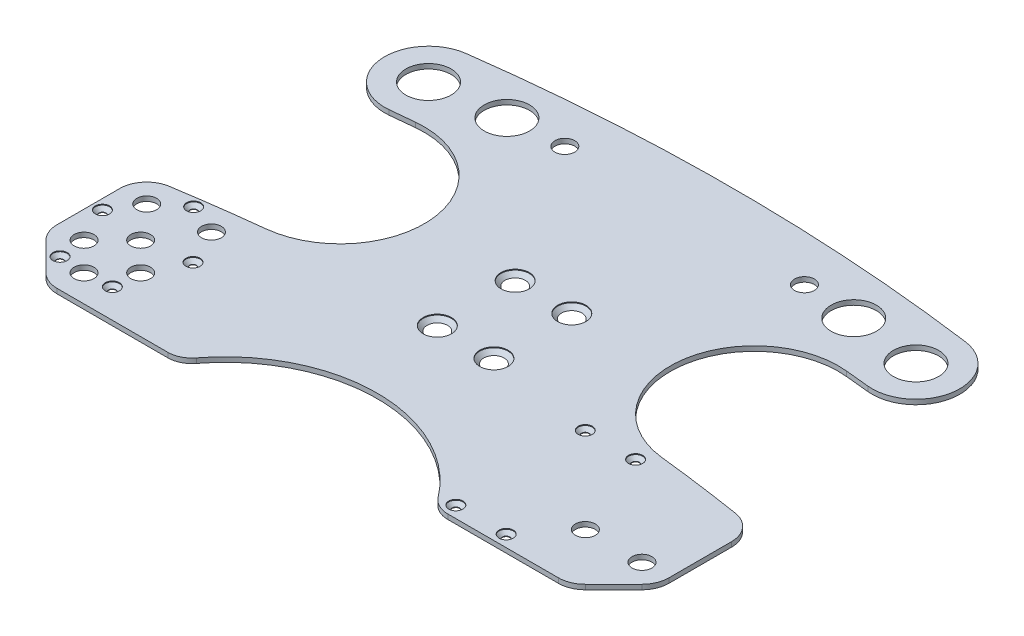
SolidWorks part; units mm, degrees
ref_plane "Front Plane" through (0, 0, 0) normal (0, 0, 1) x (1, 0, 0)
ref_plane "Top Plane" through (0, 0, 0) normal (0, 1, 0) x (1, 0, 0)
ref_plane "Right Plane" through (0, 0, 0) normal (1, 0, 0) x (0, 0, -1)
sketch "Sketch1" plane through (0, 0, 0) normal (0, 1, 0) x (1, 0, 0)
  line L1 (-120, -95) -> (120, -95)
  line L2 (-120, -95) -> (-120, 95)
  line L3 (-120, 95) -> (120, 95)
  line L4 (120, -95) -> (120, 95)
  line L5 (-120, -95) -> (120, 95) construction
  line L6 (-120, 95) -> (120, -95) construction
  line L7 (-10, 13.75) -> (10, 13.75)
  line L8 (-10, 13.75) -> (-10, -13.75)
  line L9 (-10, -13.75) -> (10, -13.75)
  line L10 (10, 13.75) -> (10, -13.75)
  line L11 (-10, 13.75) -> (10, -13.75) construction
  line L12 (-10, -13.75) -> (10, 13.75) construction
  circle A0 centre (0, 0) radius 95
  circle A1 centre (-10, 13.75) radius 2.5
  circle A2 centre (10, 13.75) radius 2.5
  circle A3 centre (10, -13.75) radius 2.5
  circle A4 centre (-10, -13.75) radius 2.5
  circle A5 centre (0, 0) radius 120
  dimension "D3" = 5
  dimension "D1" = 240
  dimension "D2" = 190
  dimension "D4" = 27.5
  dimension "D5" = 20
extrude "Boss-Extrude1" add sketch "Sketch1" along normal blind 1.7 contours A0 A4 L8 A1 L7 A2 L10 A3 L9 | A4 L9 A3 L10 A2 L7 A1 L8 | L3 A5 L1 A0 | L1 A5 L3 A0 region at (-105.6812, 0, 51.9346) region at (68.7642, 0, 68.7642) region at (-92.313, 0, 0) region at (0, 0, 0)
sketch "Sketch2" plane through (0, 1.7, 0) normal (0, 1, 0) x (1, 0, 0)
  line L0 (-81.1673, -40) -> (21.9115, -40) construction
  line L1 (-127.3056, -60) -> (138.909, -60) construction
  line L2 (-88.5406, 28.139) -> (-88.5406, -89.0376) construction
  line L3 (-88.5406, -40) -> (-88.5406, -60) construction
  line L4 (0, 21.6044) -> (0, -21.4213) construction
  line L5 (88.5406, 33.139) -> (88.5406, -84.0376) construction
  line L6 (-151.9803, -25) -> (55.006, -25) construction
  line L7 (-48.8837, 35) -> (62.426, 35) construction
  circle A0 centre (0, 0) radius 35
  circle A1 centre (0, 35) radius 2.5
  circle A2 centre (30.3109, 17.5) radius 2.5
  circle A3 centre (30.3109, -17.5) radius 2.5
  circle A4 centre (0, -35) radius 2.5
  circle A5 centre (-30.3109, -17.5) radius 2.5
  circle A6 centre (-30.3109, 17.5) radius 2.5
  circle A7 centre (-88.5406, -40) radius 3.5
  circle A8 centre (-88.5406, -50) radius 10
  circle A9 centre (-78.5406, -50) radius 3.5
  circle A10 centre (-88.5406, -60) radius 3.5
  circle A11 centre (-98.5406, -50) radius 3.5
  circle A12 centre (78.5406, -50) radius 3.5
  circle A13 centre (98.5406, -50) radius 3.5
  circle A14 centre (-98.5406, -27.8625) radius 3.5
  circle A15 centre (-78.5406, -25) radius 3.5
  circle A16 centre (0, 0) radius 45
  circle A17 centre (0, -580) radius 625
  circle A18 centre (0, -580) radius 645
  circle A19 centre (-86.0945, 59.2282) radius 8
  circle A20 centre (-61.2596, 62.0843) radius 8
  circle A21 centre (-86.0945, 59.2282) radius 15.5
  arc A22 (-73.3144, 95) -> (-73.3144, -95) centre (0, 0) ccw construction
  circle A23 centre (-61.2596, 62.0843) radius 9.5
  circle A24 centre (-86.0945, 59.2282) radius 9.5
  circle A25 centre (61.2596, 62.0843) radius 8
  circle A26 centre (86.0945, 59.2282) radius 8
  circle A27 centre (-42.3209, 63.6101) radius 3.5
  circle A28 centre (0, 0) radius 70
  circle A29 centre (42.3209, 63.6101) radius 3.5
  circle A30 centre (-98.5406, -50) radius 9.5
  circle A31 centre (42.3209, 63.6101) radius 9.5
  circle A32 centre (61.2596, 62.0843) radius 9.5
  circle A33 centre (0, -645.0455) radius 625
  point P17 (0, 0)
  point P21 (-88.5406, -50)
  point P37 (-88.5406, -50)
  point P56 (0, 65)
  point P57 (0, 45)
  point P68 (-76.6704, 60.4269)
  point P69 (-70.7097, 61.1124)
  point P81 (0, 0)
  point P85 (-98.5406, -27.8625)
  dimension "D1" = 70
  dimension "D2" = 5
  dimension "D4" = 7
  dimension "D9" = 90
  dimension "D10" = 1250
  dimension "D11" = 20
  dimension "D12" = 16
  dimension "D14" = 6
  dimension "D13" = 19
  dimension "D17" = 140
  dimension "D18" = 6
  dimension "D5" = 20
  dimension "D6" = 40
  dimension "D8" = 15
  dimension "D15" = 6
  dimension "D3" = 6
  dimension "D7" = 4
extrude "Cut-Extrude1" cut sketch "Sketch2" against normal up to next contours A7 | A9 | A10 | A11 | A12 | A13 | A14 | A15 | A19 | A20 | A25 | A26 | A27 | A29
sketch "Sketch3" plane through (0, 1.7, 0) normal (0, 1, 0) x (1, 0, 0)
  line L1 (-84.5506, 43.8053) -> (-40.7771, 48.1872)
  line L2 (0, 100.6986) -> (0, -98.8678) construction
  line L3 (-10.3445, 0) -> (20.4144, 0) construction
  line L5 (84.5506, 43.8053) -> (40.7771, 48.1872)
  line L6 (-42.3209, 63.6101) -> (0, 0) construction
  line L7 (-36.306, 26.5871) -> (-55.2257, 55.0243)
  line L8 (-10.4964, 43.7587) -> (-29.4161, 72.1959)
  line L9 (10.4964, 43.7587) -> (29.4161, 72.1959)
  line L10 (36.306, 26.5871) -> (55.2257, 55.0243)
  line L11 (-108.0406, -50) -> (-108.0406, -27.8625)
  line L13 (-73.3144, -95) -> (73.3144, -95)
  line L14 (73.3144, 95) -> (-73.3144, 95)
  line L15 (-73.3144, -95) -> (73.3144, -95)
  line L16 (73.3144, 95) -> (-73.3144, 95)
  line L17 (-69.0406, -25) -> (-69.0406, -50)
  line L18 (-71.8231, -56.7175) -> (-81.8231, -66.7175)
  line L19 (-105.2581, -56.7175) -> (-95.2581, -66.7175)
  line L20 (-42.3209, 79.1101) -> (42.3209, 79.1101)
  line L21 (-78.5406, -15.5) -> (-42.2463, -15.5)
  line L22 (0, -45) -> (111.243, -45) construction
  line L23 (-88.5406, -69.5) -> (88.5406, -69.5)
  line L24 (69.0406, -15.5) -> (45.0406, -15.5)
  line L25 (78.5406, -15.5) -> (42.2463, -15.5)
  line L27 (108.0406, -50) -> (108.0406, -27.8625)
  line L28 (105.2581, -56.7175) -> (95.2581, -66.7175)
  line L29 (69.0406, -15.5) -> (69.0406, -69.5)
  line L30 (69.0406, -69.5) -> (45.0406, -69.5)
  line L31 (45.0406, -15.5) -> (45.0406, -69.5)
  line L32 (57.0406, -15.5) -> (57.0406, -69.5) construction
  line L33 (45.0406, -42.5) -> (69.0406, -42.5) construction
  circle A0 centre (-86.0945, 59.2282) radius 15.5
  arc A1 (-73.3144, 95) -> (-73.3144, -95) centre (0, 0) ccw construction
  circle A2 centre (-42.3209, 63.6101) radius 15.5
  circle A3 centre (86.0945, 59.2282) radius 15.5
  circle A4 centre (42.3209, 63.6101) radius 15.5
  circle A5 centre (0, 0) radius 45
  circle A6 centre (-98.5406, -27.8625) radius 9.5
  circle A7 centre (-98.5406, -27.8625) radius 3.5 construction
  arc A8 (-73.3144, 95) -> (-73.3144, -95) centre (0, 0) ccw
  arc A9 (73.3144, -95) -> (73.3144, 95) centre (0, 0) ccw
  arc A10 (-73.3144, 95) -> (-73.3144, -95) centre (0, 0) ccw
  arc A11 (73.3144, -95) -> (73.3144, 95) centre (0, 0) ccw
  circle A12 centre (-78.5406, -25) radius 9.5
  circle A13 centre (-88.5406, -60) radius 9.5
  circle A14 centre (-98.5406, -50) radius 9.5
  circle A15 centre (-78.5406, -50) radius 9.5
  circle A17 centre (98.5406, -50) radius 9.5
  circle A18 centre (78.5406, -50) radius 9.5
  arc A19 (73.3144, -95) -> (73.3144, 95) centre (0, 0) ccw construction
  arc A20 (-45.0406, -69.5) -> (45.0406, -69.5) centre (0, -98.6511) cw
  circle A21 centre (98.5406, -27.8625) radius 9.5
  circle A22 centre (98.5406, -50) radius 9.5
  circle A23 centre (88.5406, -60) radius 9.5
  circle A24 centre (-73.1485, 15.1063) radius 29.692
  circle A25 centre (73.1485, 15.1063) radius 29.692
  circle A26 centre (48.1506, -19.64) radius 1.3
  circle A27 centre (65.9306, -19.64) radius 1.3
  circle A28 centre (65.9306, -65.36) radius 1.3
  circle A29 centre (48.1506, -65.36) radius 1.3
  circle A30 centre (0, -580) radius 645
  circle A31 centre (0, -580) radius 660.5
  circle A32 centre (0, -645.0455) radius 634.5
  point P20 (0, -659.5242)
  arc M45 (-73.3144, 95) -> (-73.3144, -95) centre (0, 0) ccw
  line M46 (-73.3144, -95) -> (73.3144, -95)
  arc M47 (73.3144, -95) -> (73.3144, 95) centre (0, 0) ccw
  line M48 (73.3144, 95) -> (-73.3144, 95)
  dimension "D1" = 90
  dimension "D3" = 6
  dimension "D5" = 2.6
  dimension "D4" = 24
  dimension "D6" = 17.78
  dimension "D7" = 45.72
  dimension "D2" = 0
extrude "Cut-Extrude2" cut sketch "Sketch3" against normal up to next contours A24 L1 A0 A14 L11 A6 L21 M45 | A24 | L28 A23 L23 A13 L19 A14 A10 A17 M46 M47 | A20 L23 | L5 A25 L24 L25 A21 L27 A17 A11 A3 | A25 | A30 A0 M45 | A31 A11 M48 M45 | A0 A31 A10 | A31 A3 M47 | A30 A3 M47 | A6 A32 A14 L11 M45 | A11 A32 A21 L27 A17 | A26 | A27 | A28 | A29 region at (-105.8887, 1.7, -12.959) region at (-73.1485, 1.7, -15.1063) region at (-102.839, 1.7, -59.5932) region at (-94.2652, 1.7, -72.7135) region at (0, 1.7, -86.2332) region at (-111.2756, 1.7, 31.2797) region at (0, 1.7, 81.3426) region at (0, 1.7, 59.4787) region at (73.1485, 1.7, -15.1063) region at (105.8887, 1.7, -12.959) region at (111.2756, 1.7, 31.2797) region at (94.2652, 1.7, -72.7135) region at (102.839, 1.7, -59.5932)
sketch "Sketch8" plane through (0, 1.7, 0) normal (0, 1, 0) x (1, 0, 0)
  circle A8 centre (-89.4023, -20.411) radius 1.25
  circle A9 centre (-104.5406, -37.5) radius 1.25
  circle A10 centre (-72.5406, -37.5) radius 1.25
  circle A11 centre (-97.7832, -59.2426) radius 1.25
  circle A17 centre (-79.298, -59.2426) radius 1.25
  circle A19 centre (-89.4023, -20.411) radius 1.5 construction
  circle A20 centre (-104.5406, -37.5) radius 1.5 construction
  circle A21 centre (-72.5406, -37.5) radius 1.5 construction
  circle A22 centre (-79.298, -59.2426) radius 1.5 construction
  circle A23 centre (-97.7832, -59.2426) radius 1.5 construction
  dimension "D1" = 2.5
extrude "Cut-Extrude3" cut sketch "Sketch8" against normal up to next contours A8 | A10 | A9 | A11 | A17
hole_wizard "CSK for M5 Flat Head Machine Screw1" positions "Sketch4" profile "Sketch5" countersink size "M5" standard "ANSI Metric"
sketch "Sketch4" plane through (0, 1.7, 0) normal (0, 1, 0) x (1, 0, 0)
  point P0 (-10, 13.75)
  point P3 (10, 13.75)
  point P6 (10, -13.75)
  point P9 (-10, -13.75)
sketch "Sketch5" plane through (-10, 1.7, -13.75) normal (1, 0, 0) x (0, 0, 1)
  line L0 (0, 0) -> (0, 6.5022)
  line L1 (0, 6.5022) -> (2.5, 5)
  line L2 (2.5, 5) -> (2.5, 2.8)
  line L3 (2.5, 2.8) -> (5, 0.3)
  line L4 (5, 0.3) -> (5, 0)
  line L6 (5, 0) -> (0, 0)
  line L7 (-2.5, 2.8) -> (-5, 0.3) construction
  line L10 (0, 6.5022) -> (-2.5, 5) construction
  line L11 (0, -6.35) -> (0, 107.95) construction
  dimension "Hole Dia." = 5
  dimension "Hole Depth" = 5
  dimension "C'Sink Dia." = 10
  dimension "C'Sink Angle" = 90
  dimension "Drill Angle" = 118
  dimension "Head Clearance" = 0.3
hole_wizard "CSK for M2.5 Flat Head Machine Screw1" positions "Sketch6" profile "Sketch7" countersink size "M2.5" standard "ANSI Metric"
sketch "Sketch6" plane through (0, 1.7, 0) normal (0, 1, 0) x (1, 0, 0)
  point P0 (48.1506, -19.64)
  point P3 (65.9306, -19.64)
  point P6 (65.9306, -65.36)
  point P9 (48.1506, -65.36)
  point P12 (-89.4023, -20.411)
  point P15 (-72.5406, -37.5)
  point P18 (-104.5406, -37.5)
  point P21 (-97.7832, -59.2426)
  point P24 (-79.298, -59.2426)
sketch "Sketch7" plane through (48.1506, 1.7, 19.64) normal (1, 0, 0) x (0, 0, 1)
  line L0 (0, 0) -> (0, 5.7511)
  line L1 (0, 5.7511) -> (1.25, 5)
  line L2 (1.25, 5) -> (1.25, 1.55)
  line L3 (1.25, 1.55) -> (2.5, 0.3)
  line L4 (2.5, 0.3) -> (2.5, 0)
  line L6 (2.5, 0) -> (0, 0)
  line L7 (-1.25, 1.55) -> (-2.5, 0.3) construction
  line L10 (0, 5.7511) -> (-1.25, 5) construction
  line L11 (0, -6.35) -> (0, 107.95) construction
  dimension "Hole Dia." = 2.5
  dimension "Hole Depth" = 5
  dimension "C'Sink Dia." = 5
  dimension "C'Sink Angle" = 90
  dimension "Drill Angle" = 118
  dimension "Head Clearance" = 0.3
fillet "Fillet1" radius 8.5 2 edges at (45.0406, 0.85, 69.5) (-45.0406, 0.85, 69.5)
